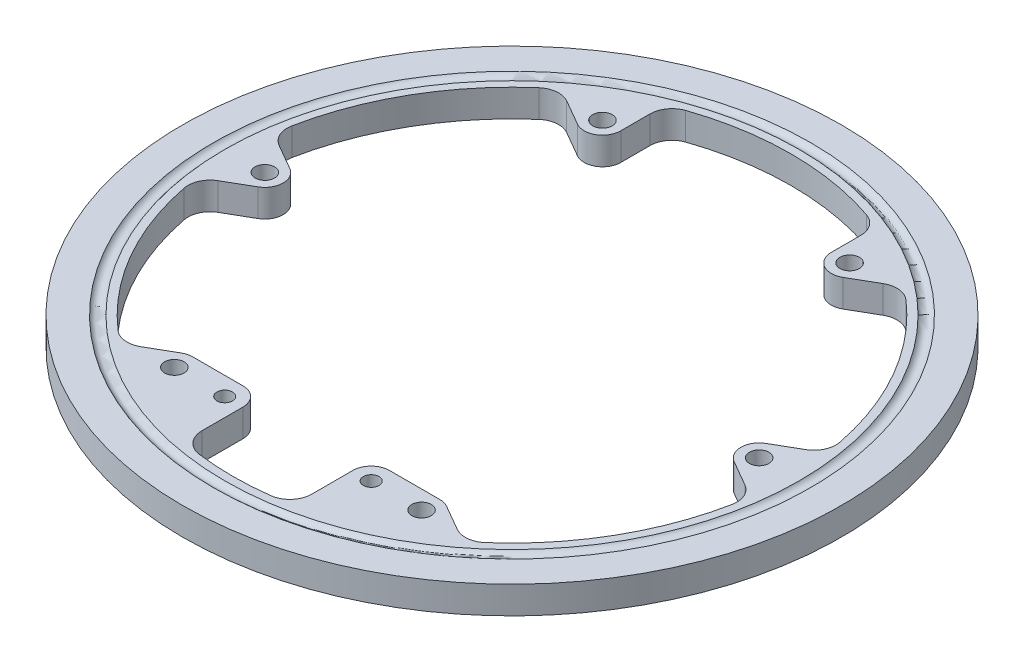
SolidWorks part; units mm, degrees
ref_plane "Front Plane" through (0, 0, 0) normal (0, 0, 1) x (1, 0, 0)
ref_plane "Top Plane" through (0, 0, 0) normal (0, 1, 0) x (1, 0, 0)
ref_plane "Right Plane" through (0, 0, 0) normal (1, 0, 0) x (0, 0, -1)
sketch "Sketch1" plane through (0, 0, 0) normal (0, 1, 0) x (1, 0, 0)
  line L8 (0, 0) -> (-51.7328, 0) construction
  circle A0 centre (0, 0) radius 114.3
  circle A1 centre (0, 0) radius 96.8375
  point P3 (-75.7522, -62.5631)
  point P7 (75.7522, -58.351)
  point P12 (23.9758, -86.9061)
  point P13 (23.1291, -91.8533)
  point P15 (40.5831, 87.9234)
  dimension "D1" = 228.6
  dimension "D2" = 193.675
extrude "Boss-Extrude1" add sketch "Sketch1" along normal blind 9.525
sketch "Sketch3" plane through (0, 0, 0) normal (0, -1, 0) x (1, 0, 0)
  line L0 (0, 0) -> (96.8375, 0) construction
  line L1 (95.9303, -13.2244) -> (82.55, -5.4993)
  line L2 (82.55, 5.4993) -> (95.9303, 13.2244)
  circle A0 centre (0, 0) radius 96.8375 construction
  arc A1 (95.9303, -13.2244) -> (95.9303, 13.2244) centre (0, 0) ccw
  arc A2 (82.55, -5.4993) -> (82.55, 5.4993) centre (85.725, 0) cw
  dimension "D1" = 6.35
  dimension "D2" = 60
  dimension "D3" = 85.725
extrude "Boss-Extrude2" add sketch "Sketch3" against normal up to surface (9.525 mm away) up to face at (0, 9.525, 114.3)
fillet "Fillet2" radius 7.62 2 edges at (95.9303, 4.7625, 13.2244) (95.9303, 4.7625, -13.2244)
pattern_circular "CirPattern1" count 6 over 360 about axis through (0, 9.525, 0) along (0, -1, 0) of "Boss-Extrude2", "Fillet2" reverse direction yes
sketch "Sketch7" plane through (0, 9.525, 0) normal (0, 1, 0) x (1, 0, 0)
  line L0 (0, 0) -> (0, -74.24) construction
  line L1 (0, -74.24) -> (25.4, -74.24) construction
  line L2 (0, -74.24) -> (-25.4, -74.24) construction
  line L3 (42.8625, -67.89) -> (25.4, -67.89)
  line L4 (-42.8625, -67.89) -> (-25.4, -67.89)
  line L5 (19.05, -74.24) -> (19.05, -94.9452)
  line L6 (-19.05, -94.9452) -> (-19.05, -74.24)
  line L7 (36.5125, -84.4096) -> (36.5125, -74.24) construction
  line L8 (-36.5125, -74.24) -> (-36.5125, -84.4096) construction
  line L9 (-36.5125, -74.24) -> (-36.5125, -84.4096)
  line L10 (36.5125, -84.4096) -> (36.5125, -74.24)
  arc A0 (25.4, -67.89) -> (19.05, -74.24) centre (25.4, -74.24) ccw
  arc A1 (-19.05, -74.24) -> (-25.4, -67.89) centre (-25.4, -74.24) ccw
  arc A2 (-36.5125, -74.24) -> (-46.0375, -68.7408) centre (-42.8625, -74.24) ccw construction
  arc A3 (46.0375, -68.7408) -> (36.5125, -74.24) centre (42.8625, -74.24) ccw construction
  arc A4 (-31.3602, -91.619) -> (31.3602, -91.619) centre (0, 0) ccw construction
  arc A5 (19.05, -74.24) -> (25.4, -67.89) centre (25.4, -74.24) ccw construction
  arc A6 (-25.4, -67.89) -> (-19.05, -74.24) centre (-25.4, -74.24) ccw construction
  arc A7 (31.3602, -91.619) -> (36.5125, -84.4096) centre (28.8925, -84.4096) ccw construction
  arc A9 (-36.5125, -84.4096) -> (-31.3602, -91.619) centre (-28.8925, -84.4096) ccw construction
  arc A10 (-36.5125, -84.4096) -> (-31.3602, -91.619) centre (-28.8925, -84.4096) ccw
  arc A11 (-36.5125, -74.24) -> (-42.8625, -67.89) centre (-42.8625, -74.24) ccw
  arc A12 (-31.3602, -91.619) -> (-19.05, -94.9452) centre (0, 0) ccw
  arc A13 (31.3602, -91.619) -> (36.5125, -84.4096) centre (28.8925, -84.4096) ccw
  arc A14 (42.8625, -67.89) -> (36.5125, -74.24) centre (42.8625, -74.24) ccw
  arc A15 (19.05, -94.9452) -> (31.3602, -91.619) centre (0, 0) ccw
  dimension "D1" = 50.8
  dimension "D3" = 20.7052
sketch "Sketch4" plane through (0, 0, 0) normal (0, -1, 0) x (-1, 0, 0)
  point P0 (-42.8625, 74.24)
  point P3 (42.8625, 74.24)
  point P6 (85.725, 0)
  point P9 (42.8625, -74.24)
  point P12 (-42.8625, -74.24)
  point P15 (-85.725, 0)
hole_wizard "1/4 Clearance Hole1" positions "Sketch4" profile "Sketch6" hole size "1/4" standard "ANSI Inch" end condition through all
sketch "Sketch6" plane through (42.8625, 0, -74.24) normal (1, 0, 0) x (0, 0, -1)
  line L0 (0, 0) -> (0, 9.525)
  line L1 (0, 9.525) -> (3.3782, 9.525)
  line L2 (3.3782, 9.525) -> (3.3782, 0)
  line L5 (3.3782, 0) -> (0, 0)
  line L11 (0, -6.35) -> (0, 107.95) construction
  dimension "Thru Hole Dia." = 6.7564
  dimension "Thru Hole Depth" = 9.525
sketch "Sketch2" plane through (0, 0, 0) normal (1, 0, 0) x (0, 0, -1)
  line L0 (-114.3, 4.7625) -> (-68.0352, 4.7625) construction
  line L1 (-114.3, 9.525) -> (-114.3, 0) construction
  line L2 (-114.3, 0) -> (114.3, 0) construction
  line L3 (0, 0) -> (0, 24.7794) construction
  circle A0 centre (-101.6, 10.795) radius 2.3813
  circle A1 centre (-101.6, -1.27) radius 2.3813
  dimension "D3" = 4.7625
  dimension "D1" = 12.065
  dimension "D2" = 1.27
  dimension "D4" = 203.2
revolve "Cut-Revolve1" cut sketch "Sketch2" angle 360 about L3
extrude "Boss-Extrude3" add sketch "Sketch7" against normal up to surface (9.525 mm away) up to face at (85.725, 0, -3.3782)
fillet "Fillet3" radius 7.62 2 edges at (-19.05, 4.7625, 94.9452) (19.05, 4.7625, 94.9452)
sketch "Sketch8" plane through (0, 9.525, 0) normal (0, 1, 0) x (1, 0, 0)
  point P0 (25.4, -74.24)
  point P3 (-25.4, -74.24)
hole_wizard "1/4-28 Tapped Hole1" positions "Sketch8" profile "Sketch9" tap size "1/4-28" standard "ANSI Inch" end condition through all
sketch "Sketch9" plane through (25.4, 9.525, 74.24) normal (1, 0, 0) x (0, 0, 1)
  line L0 (0, 0) -> (0, 9.525)
  line L1 (0, 9.525) -> (2.7051, 9.525)
  line L2 (2.7051, 9.525) -> (2.7051, 0)
  line L5 (2.7051, 0) -> (0, 0)
  line L11 (0, -6.35) -> (0, 107.95) construction
  dimension "Thru Tap Drill Dia." = 5.4102
  dimension "Thru Tap Drill Depth" = 9.525
